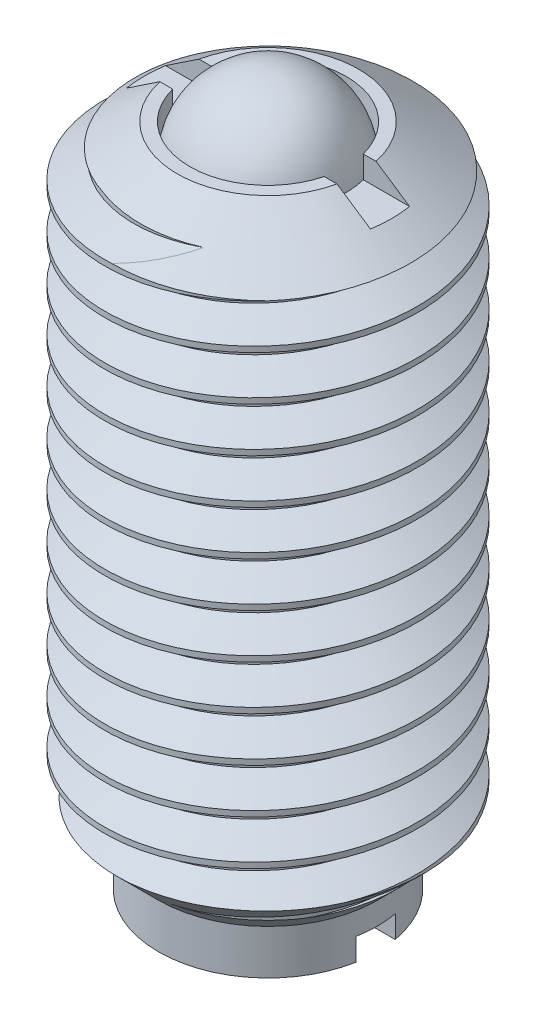
SolidWorks part; units mm, degrees
ref_plane "Front" through (0, 0, 0) normal (0, 0, 1) x (1, 0, 0)
ref_plane "Top" through (0, 0, 0) normal (0, 1, 0) x (1, 0, 0)
ref_plane "Right" through (0, 0, 0) normal (1, 0, 0) x (0, 0, -1)
sketch "Sketch24" plane through (0, 0, 0) normal (1, 0, 0) x (0, 0, -1)
  line L0 (3.175, 6.7437) -> (-3.175, 6.7437) construction
  line L1 (0, 6.7437) -> (3.175, 6.7437)
  line L2 (0, 6.7437) -> (0, -6.7437)
  line L3 (0, -6.7437) -> (3.175, -6.7437)
  line L4 (3.175, 6.7437) -> (3.175, -6.7437)
  point P5 (3.175, 2.6616)
  dimension "Body Length" = 13.4874
  dimension "Screw Dia" = 6.35
  dimension "D1" = 4.0821
revolve "Revolve1" add sketch "Sketch24" angle 360 about L2
sketch "Sketch37" plane through (0, 6.7437, 0) normal (0, 1, 0) x (1, 0, 0)
  circle A1 centre (0, 0) radius 3.175
  circle A2 centre (0, 0) radius 3.175
  dimension "D1" = 0
curve "Helix/Spiral1" pitch 0.9071 height 14.3945 turns 15.868 parameters "pitch"=0.9071
sketch "Sketch38" plane through (0, 0, 0) normal (1, 0, 0) x (0, 0, -1)
  line L0 (-3.175, 7.5375) -> (-3.175, 6.7437)
  line L1 (-3.175, 7.5375) -> (-2.5858, 7.1973)
  line L2 (-2.5858, 7.1973) -> (-2.5858, 7.0839)
  line L3 (-2.5858, 7.0839) -> (-3.175, 6.7437)
  line L4 (-2.5858, 7.1406) -> (-3.175, 7.1406) construction
  line L5 (-2.8804, 7.3674) -> (-2.8804, 6.9138) construction
  line L6 (3.175, 6.7437) -> (-3.175, 6.7437) construction
  line L7 (0, 0) -> (0, 6.7437) construction
  dimension "D1" = 0.1134
  dimension "D2" = 0.4536
  dimension "D3" = 60
  dimension "D4" = 0.5892
  dimension "D5" = 2.5858
  dimension "D6" = 0.2946
sweep "Cut-Sweep1" cut profiles "Sketch38" path "Helix/Spiral1" align with end faces yes
sketch "Sketch26" plane through (0, 0, 0) normal (1, 0, 0) x (0, 0, -1)
  line L0 (0, -5.395) -> (0, 6.7437)
  line L1 (0, 6.7437) -> (0, -6.7437) construction
  line L2 (0, 6.7437) -> (1.5875, 6.7437)
  line L3 (1.5875, 6.7437) -> (1.5875, -5.395)
  line L5 (1.5875, -5.395) -> (0, -5.395)
  line L7 (1.5875, 6.7437) -> (-1.5875, 6.7437) construction
  line L8 (3.175, 6.7437) -> (-3.175, 6.7437) construction
  dimension "D1" = 1.3487
  dimension "Ball Dia" = 3.175
revolve "Cut-Revolve10" cut sketch "Sketch26" angle 360 about L0
sketch "Sketch31" plane through (0, 0, 0) normal (1, 0, 0) x (0, 0, -1)
  line L0 (3.175, -6.7437) -> (2.2225, -6.7437)
  line L1 (3.175, 6.7437) -> (3.175, -6.7437) construction
  line L2 (2.2225, -6.7437) -> (2.2225, -5.8366)
  line L3 (0, 0) -> (0, -14.5366) construction
  line L4 (2.2225, -5.8366) -> (3.175, -4.8841)
  line L5 (0, 0) -> (3.175, 0) construction
  line L14 (3.175, 6.7437) -> (1.8415, 6.7437)
  line L15 (0, 6.7437) -> (3.175, 6.7437) construction
  line L16 (1.8415, 6.7437) -> (3.175, 5.8366)
  line L17 (3.175, 5.8366) -> (3.175, 6.7437)
  line L18 (3.175, -4.8841) -> (3.175, -6.7437)
  dimension "D1" = 0.254
  dimension "D2" = 45
  dimension "D3" = 0.9071
  dimension "D4" = 2.2225
revolve "Cut-Revolve13" cut sketch "Sketch31" angle 360 about L2
sketch "Sketch28" plane through (0, 0, 0) normal (1, 0, 0) x (0, 0, -1)
  line L0 (2.2225, -6.2901) -> (0.3969, -6.2901) construction
  line L1 (-0.3969, -6.7437) -> (0.3969, -6.7437)
  line L2 (-0.3969, -6.7437) -> (-0.3969, -6.2901)
  line L3 (-0.3969, -6.2901) -> (0.3969, -6.2901)
  line L4 (0.3969, -6.7437) -> (0.3969, -6.2901)
  line L5 (3.175, 6.7437) -> (-3.175, 6.7437) construction
  line L6 (-0.3969, 6.7437) -> (0.3969, 6.7437)
  line L7 (-0.3969, 6.7437) -> (-0.3969, 6.2901)
  line L8 (-0.3969, 6.2901) -> (0.3969, 6.2901)
  line L9 (0.3969, 6.7437) -> (0.3969, 6.2901)
  line L10 (2.2225, -6.7437) -> (2.2225, -5.8366) construction
  dimension "D1" = 0.7937
extrude "Cut-Extrude11" cut sketch "Sketch28" against normal through all and the other way through all
sketch "Sketch27" plane through (0, 0, 0) normal (1, 0, 0) x (0, 0, -1)
  line L0 (0, 6.7437) -> (0, -6.7437) construction
  line L1 (1.5875, 6.7437) -> (1.5875, -5.395) construction
  line L2 (0, -6.7437) -> (0, 4.4577) construction
  line L3 (0, 7.6327) -> (0, 4.4577)
  circle A0 centre (0, 6.0452) radius 1.5875 construction
  arc A1 (0, 7.6327) -> (0, 4.4577) centre (0, 6.0452) cw
  dimension "Ball Projection" = 0.889
revolve "Revolve2" add sketch "Sketch27" angle 360 about L3
ref_plane "Plane1" [suppressed] through (-1.4224, 0, 0) normal (1, 0, 0) x (0, 0, -1)
sketch "Sketch21" [suppressed] plane through (-1.4224, 0, 0) normal (1, 0, 0) x (0, 0, -1)
  line L0 (0, -1.7183) -> (0, -3.2804) construction
  line L2 (1.4224, 2.3749) -> (-1.4224, 2.3749) construction
  line L3 (0, 2.3749) -> (0, -2.3749) construction
  ellipse E0 centre (0, -0.4661) end of major axis (0, 0.4585) minor radius 0.7112
  dimension "D5" = 3.175
  dimension "D6" = 4.1275
  dimension "D7" = 3.2853
sketch "Sketch41" [suppressed] plane through (-1.4224, 0, 0) normal (1, 0, 0) x (0, 0, -1)
  ellipse E1 centre (0, -0.4661) end of major axis (0, 0.4585) minor radius 0.7112
  ellipse E2 centre (0, -0.4661) end of major axis (0, 0.4585) minor radius 0.7112
  dimension "D1" = 0
sketch "Sketch43" [suppressed] plane through (0, 0, 0) normal (1, 0, 0) x (0, 0, -1)
  ellipse E1 centre (0, -0.4661) end of major axis (0, 0.4585) minor radius 0.7112
  ellipse E2 centre (0, -0.4661) end of major axis (0, 0.4585) minor radius 0.7112
  dimension "D1" = 0
extrude "Extrude9" [suppressed] cut sketch "Sketch43" against normal through all
sketch "Sketch44" [suppressed] plane through (0, 0, 0) normal (1, 0, 0) x (0, 0, -1)
  ellipse E1 centre (0, -0.4661) end of major axis (0, 0.4585) minor radius 0.7112
  ellipse E2 centre (0, -0.4661) end of major axis (0, 0.4585) minor radius 0.7112
  dimension "D1" = 0
extrude "Extrude10" [suppressed] add sketch "Sketch44" against normal blind 2.5858 separate body
dome "Dome1" [suppressed] faces to dome 1 distance 0.2946 parameters "D1"=0.2946
sketch "Sketch45" plane through (0, 0, 0) normal (0, 1, 0) x (1, 0, 0)
  circle A0 centre (0, 0) radius 1.5875
  arc A1 (-1.5371, -0.3969) -> (1.5371, -0.3969) centre (0, 0) ccw construction
extrude "Extrude11" [suppressed] cut sketch "Sketch45" against normal through all and the other way through all
equation "\"D1@Sketch26\" = \"Body Length@Sketch24\"*.1"
equation "\"D1@Sketch28\" = \"Screw Dia@Sketch24\"/8"
equation "\"D1@Sketch38\" = \"pitch@Helix/Spiral1\"*.125"
equation "\"D2@Sketch38\" = \"pitch@Helix/Spiral1\"*.50"
equation "\"D3@Helix/Spiral1\" = \"Body Length@Sketch24\"+\"pitch@Helix/Spiral1\""
equation "\"D3@Sketch31\" = \"pitch@Helix/Spiral1\""
equation "\"D4@Sketch31\" = (\"Screw Dia@Sketch24\"/2)*.7"
equation "\"D5@Sketch21\" = \"Screw Dia@Sketch24\"*.50"
equation "\"D6@Sketch21\" = \"D5@Sketch21\"*1.3"
equation "\"D7@Sketch21\" = \"pitch@Helix/Spiral1\"*3.62154"
equation "\"D1@Sketch24\" = \"pitch@Helix/Spiral1\"*4.50"
equation "\"D1@Plane1\" = \"Screw Dia@Sketch24\"/2"
equation "\"D1@Extrude10\" = \"D5@Sketch38\""
equation "\"D1@Dome1\" = \"D6@Sketch38\""
